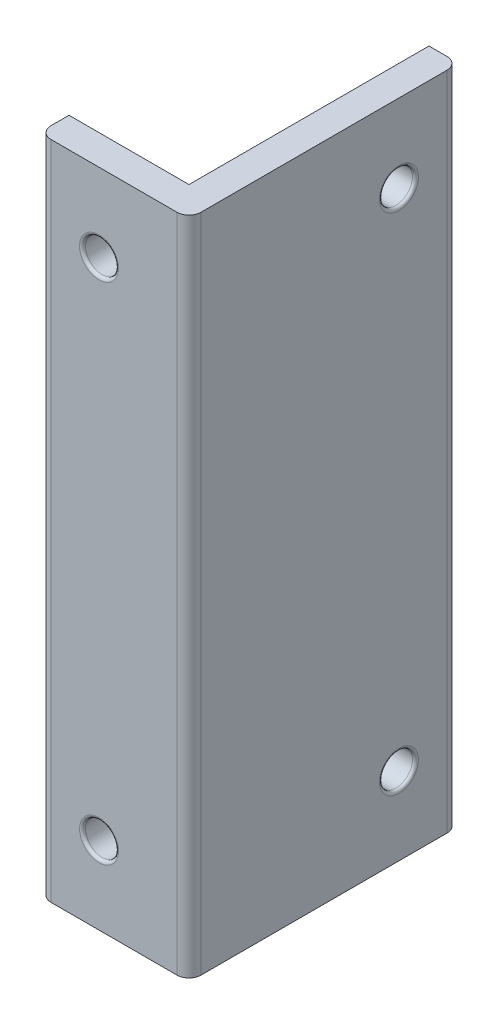
SolidWorks part; units mm, degrees
ref_plane "Front Plane" through (0, 0, 0) normal (0, 0, 1) x (1, 0, 0)
ref_plane "Top Plane" through (0, 0, 0) normal (0, 1, 0) x (1, 0, 0)
ref_plane "Right Plane" through (0, 0, 0) normal (1, 0, 0) x (0, 0, -1)
sketch "Sketch1" plane through (0, 0, 0) normal (0, 1, 0) x (1, 0, 0)
  line L0 (7.5, 2.5) -> (12.5, 2.5) construction
  line L1 (-12.5, -2.5) -> (12.5, -2.5)
  line L2 (-12.5, -2.5) -> (-12.5, 2.5)
  line L3 (-12.5, 2.5) -> (7.5, 2.5)
  line L4 (12.5, -2.5) -> (12.5, 2.5)
  line L6 (-12.5, 2.5) -> (12.5, -2.5) construction
  line L8 (12.5, 2.5) -> (12.5, 42.5)
  line L9 (12.5, 42.5) -> (7.5, 42.5)
  line L10 (7.5, 2.5) -> (7.5, 42.5)
  point P0 (0, 0)
  point P9 (0, 0)
  dimension "D1" = 20
  dimension "D2" = 5
  dimension "D3" = 5
  dimension "D4" = 40
extrude "Boss-Extrude1" add sketch "Sketch1" along normal blind 110.14
sketch "Sketch2" plane through (0, 0, 2.5) normal (0, 0, 1) x (1, 0, 0)
  line L0 (7.5, 97.14) -> (-12.5, 97.14) construction
  line L2 (-12.5, 110.14) -> (-12.5, 0) construction
  line L3 (12.5, 110.14) -> (12.5, 0) construction
  line L4 (-12.5, 110.14) -> (12.5, 110.14) construction
  line L5 (12.5, 55.07) -> (-12.5, 55.07) construction
  circle A0 centre (-2.5, 97.14) radius 2.75
  circle A2 centre (-2.5, 13) radius 2.75
  dimension "D3" = 5.5
  dimension "D1" = 5
  dimension "D2" = 13
extrude "Cut-Extrude1" cut sketch "Sketch2" against normal through all
sketch "Sketch3" plane through (12.5, 0, 0) normal (1, 0, 0) x (0, 0, -1)
  line L0 (-2.5, 110.14) -> (42.5, 110.14) construction
  line L8 (2.5, 110.14) -> (2.5, 0) construction
  line L9 (2.5, 110.14) -> (2.5, 0) construction
  line L10 (2.5, 55.07) -> (42.5, 55.07) construction
  line L11 (42.5, 110.14) -> (42.5, 0) construction
  circle A0 centre (32.5, 97.14) radius 2.75
  circle A1 centre (32.5, 13) radius 2.75
  dimension "D1" = 5.5
  dimension "D2" = 13
  dimension "D3" = 30
extrude "Cut-Extrude2" cut sketch "Sketch3" against normal through all
fillet "Fillet1" radius 0.5 8 edges at (7.5, 97.14, -35.25) (12.5, 97.14, -35.25) (7.5, 13, -35.25) (12.5, 13, -29.75) (0.25, 13, -2.5) (-5.25, 13, 2.5) (0.25, 97.14, -2.5) (0.25, 97.14, 2.5)
fillet "Fillet2" radius 2 3 edges at (12.5, 55.07, -42.5) (-12.5, 55.07, 2.5) (12.5, 55.07, 2.5)
